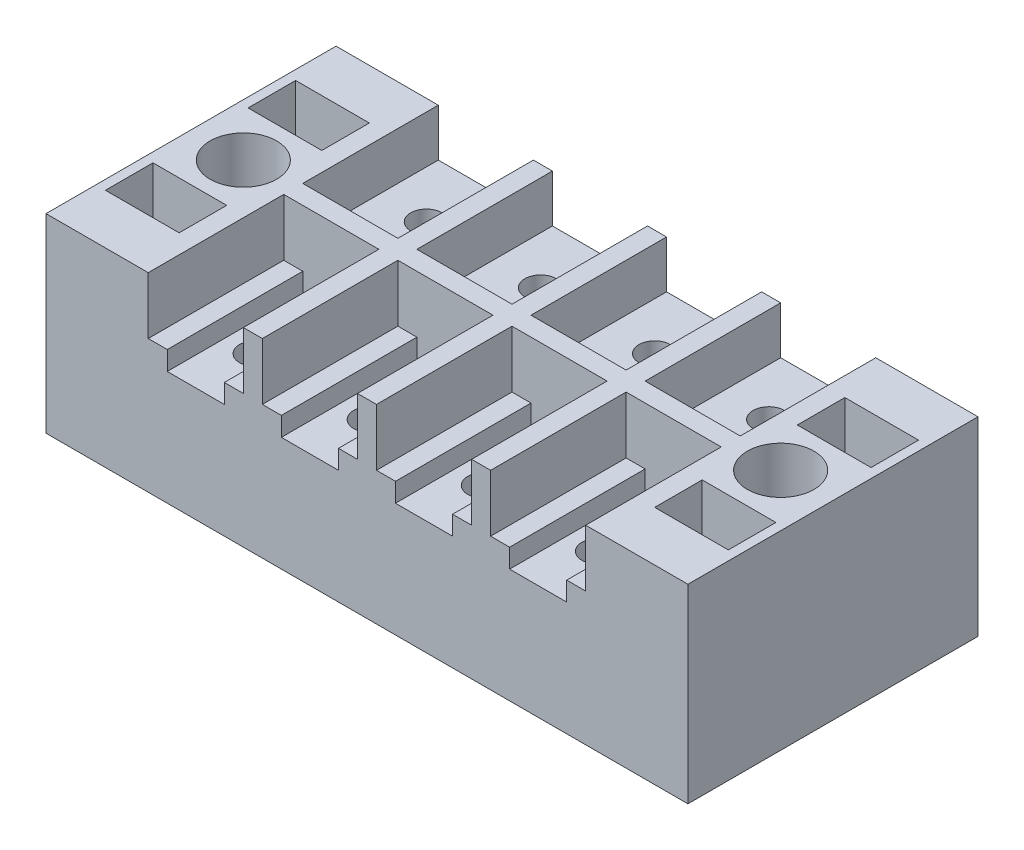
SolidWorks part; units mm, degrees
ref_plane "前视基准面" through (0, 0, 0) normal (0, 0, 1) x (1, 0, 0)
ref_plane "上视基准面" through (0, 0, 0) normal (0, 1, 0) x (1, 0, 0)
ref_plane "右视基准面" through (0, 0, 0) normal (1, 0, 0) x (0, 0, -1)
other "Configuration Table"
sketch "草图1" plane through (0, 0, 0) normal (0, 1, 0) x (1, 0, 0)
  line L0 (-57.3899, 0) -> (47.4284, 0) construction
  line L1 (33.75, -15.25) -> (-33.75, -15.25)
  line L2 (33.75, -15.25) -> (33.75, 15.25)
  line L3 (33.75, 15.25) -> (-33.75, 15.25)
  line L4 (-33.75, -15.25) -> (-33.75, 15.25)
  line L5 (33.75, -15.25) -> (-33.75, 15.25) construction
  line L6 (33.75, 15.25) -> (-33.75, -15.25) construction
  line L7 (0, 27.679) -> (0, -18.5105) construction
  line L8 (-13, -1) -> (-13, -15.25)
  line L9 (-23, -1) -> (-13, -1)
  line L10 (-1, 15.25) -> (-1, 1)
  line L11 (1, 15.25) -> (1, 1)
  line L12 (-12, 15.25) -> (-12, -15.25) construction
  line L13 (12, 15.25) -> (12, -15.25) construction
  line L14 (-24, 15.25) -> (-24, -15.25) construction
  line L15 (24, 15.25) -> (24, -15.25) construction
  line L16 (-23, 15.25) -> (-23, -15.25)
  line L17 (-13, 15.25) -> (-13, 1)
  line L18 (-25, 15.25) -> (-25, 1.299)
  line L19 (-11, 15.25) -> (-11, 1)
  line L20 (25, 15.25) -> (25, 1.299)
  line L21 (23, 15.25) -> (23, -15.25)
  line L22 (13, 15.25) -> (13, 1)
  line L23 (11, 15.25) -> (11, 1)
  line L24 (-25, -1.299) -> (-25, -15.25)
  line L25 (-23, 1) -> (-13, 1)
  line L26 (-11, 1) -> (-1, 1)
  line L27 (-11, -1) -> (-11, -15.25)
  line L28 (-11, -1) -> (-1, -1)
  line L29 (1, -1) -> (11, -1)
  line L30 (-1, -1) -> (-1, -15.25)
  line L31 (1, -1) -> (1, -15.25)
  line L32 (1, 1) -> (11, 1)
  line L33 (11, -1) -> (11, -15.25)
  line L34 (13, 1) -> (23, 1)
  line L35 (13, -1) -> (13, -15.25)
  line L36 (25, -1.299) -> (25, -15.25)
  line L37 (13, -1) -> (23, -1)
  line L38 (-32.75, -10) -> (-25, -10)
  line L39 (-32.75, 5) -> (-25, 5)
  line L40 (-32.75, 5) -> (-32.75, 10)
  line L41 (-32.75, 10) -> (-25, 10)
  line L42 (-25, 5) -> (-25, 10)
  line L43 (-25, -5) -> (-25, -10)
  line L44 (-32.75, -5) -> (-25, -5)
  line L45 (-32.75, -5) -> (-32.75, -10)
  line L46 (32.75, 10) -> (25, 10)
  line L47 (25, 5) -> (25, 10)
  line L48 (32.75, 5) -> (25, 5)
  line L49 (32.75, 5) -> (32.75, 10)
  line L50 (32.75, -5) -> (32.75, -10)
  line L51 (32.75, -5) -> (25, -5)
  line L52 (25, -5) -> (25, -10)
  line L53 (32.75, -10) -> (25, -10)
  line L54 (-18, 1) -> (-18, 16.7554) construction
  line L55 (-18, 1) -> (-18, -15.8397) construction
  line L56 (-6, 1) -> (-6, 16.7554) construction
  line L57 (-6, 1) -> (-6, -15.8397) construction
  line L58 (6, 1) -> (6, 16.7554) construction
  line L59 (6, 1) -> (6, -15.8397) construction
  line L60 (18, 1) -> (18, 16.7554) construction
  line L61 (18, 1) -> (18, -15.8397) construction
  circle A0 centre (-28.25, 0) radius 3.5
  circle A1 centre (-28.25, 0) radius 2.1
  circle A2 centre (28.25, 0) radius 2.1
  circle A3 centre (28.25, 0) radius 3.5
  point P0 (0, 0)
  dimension "D3" = 7
  dimension "D4" = 4.2
  dimension "D1" = 67.5
  dimension "D2" = 30.5
  dimension "D5" = 56.5
  dimension "D6" = 1
  dimension "D7" = 2
  dimension "D8" = 12
  dimension "D9" = 5
  dimension "D10" = 10
extrude "凸台-拉伸1" add sketch "草图1" against normal blind 20 contours L3 L4 L1 L2 | L40 L39 L42 L41 | L38 L43 L44 L45 | L50 L53 L52 L51 | L46 L47 L48 L49
extrude "切除-拉伸1" cut sketch "草图1<3>" against normal blind 13 contours A0 | A3
sketch "草图1<3>" plane through (0, 0, 0) normal (0, 1, 0) x (1, 0, 0) same geometry as "草图1"
extrude "切除-拉伸2" cut sketch "草图1<4>" against normal through all contours A1 | A2
sketch "草图1<4>" plane through (0, 0, 0) normal (0, 1, 0) x (1, 0, 0) same geometry as "草图1"
extrude "切除-拉伸3" cut sketch "草图1<5>" against normal blind 6 contours L9 L16 L1 L8 | L30 L28 L27 L1 | L33 L29 L31 L1 | L37 L35 L1 L21 region at (18, 0, 8.125) region at (6, 0, 8.125) region at (-6, 0, 8.125) region at (-18, 0, 8.125)
sketch "草图1<5>" plane through (0, 0, 0) normal (0, 1, 0) x (1, 0, 0) same geometry as "草图1"
extrude "切除-拉伸4" cut sketch "草图1<6>" against normal blind 5 contours L16 L25 L17 L3 | L19 L26 L10 L3 | L11 L32 L23 L3 | L22 L34 L21 L3 region at (18, 0, -8.125) region at (6, 0, -8.125) region at (-6, 0, -8.125) region at (-18, 0, -8.125)
sketch "草图1<6>" plane through (0, 0, 0) normal (0, 1, 0) x (1, 0, 0) same geometry as "草图1"
sketch "草图2" plane through (0, 0, 15.25) normal (0, 0, 1) x (1, 0, 0)
  line L0 (-18, -6) -> (-18, -7.8376) construction
  line L1 (-13, -6) -> (-23, -6) construction
  line L2 (-9, -6) -> (-9, -8)
  line L3 (-21, -6) -> (-15, -6)
  line L4 (-21, -6) -> (-21, -8)
  line L5 (-21, -8) -> (-15, -8)
  line L6 (-15, -6) -> (-15, -8)
  line L7 (-9, -6) -> (-3, -6)
  line L8 (-3, -6) -> (-3, -8)
  line L9 (-9, -8) -> (-3, -8)
  line L10 (3, -6) -> (3, -8)
  line L11 (3, -6) -> (9, -6)
  line L12 (9, -6) -> (9, -8)
  line L13 (3, -8) -> (9, -8)
  line L14 (15, -6) -> (15, -8)
  line L15 (15, -6) -> (21, -6)
  line L16 (21, -6) -> (21, -8)
  line L17 (15, -8) -> (21, -8)
  dimension "D1" = 6
  dimension "D2" = 2
  dimension "D3" = 4
extrude "切除-拉伸5" cut sketch "草图2" against normal up to surface (14.25 mm away) up to face at (-18, -3, 1)
sketch "草图3" plane through (0, -20, 0) normal (0, -1, 0) x (1, 0, 0)
  line L5 (33.75, 15.25) -> (-33.75, 15.25) construction
  line L6 (-23, -15.25) -> (-23, 15.25) construction
  line L8 (-18, 1) -> (-18, 15.25) construction
  line L9 (-23, 1) -> (-13, 1) construction
  line L10 (-23, 3.75) -> (23, 3.75)
  line L11 (-23, 3.75) -> (-23, 13.75)
  line L12 (-23, 13.75) -> (23, 13.75)
  line L13 (23, 3.75) -> (23, 13.75)
  line L14 (23, -15.25) -> (23, 15.25) construction
  line L15 (-35.8054, 0) -> (37.4721, 0) construction
  line L16 (-57.3899, 0) -> (47.4284, 0) construction
  line L17 (-23, -13.75) -> (23, -13.75)
  line L18 (23, -3.75) -> (23, -13.75)
  line L19 (-23, -3.75) -> (23, -3.75)
  line L20 (-23, -3.75) -> (-23, -13.75)
  line L22 (-23, -2.55) -> (23, -2.55)
  line L23 (-23, -2.55) -> (-23, 2.55)
  line L24 (-23, 2.55) -> (23, 2.55)
  line L25 (23, -2.55) -> (23, 2.55)
  circle A0 centre (-18, 9.25) radius 3.5
  circle A1 centre (-6, 9.25) radius 3.5
  circle A2 centre (6, 9.25) radius 3.5
  circle A3 centre (18, 9.25) radius 3.5
  circle A4 centre (-6, -8.25) radius 3.5
  circle A5 centre (6, -8.25) radius 3.5
  circle A6 centre (18, -8.25) radius 3.5
  circle A7 centre (-18, -8.25) radius 3.5
  dimension "D1" = 7
  dimension "D2" = 6
  dimension "D3" = 4
  dimension "D5" = 1.5
  dimension "D6" = 10
  dimension "D7" = 1.2
  dimension "D4" = 2
extrude "切除-拉伸6" cut sketch "草图3" against normal blind 7.5 contours L10 L13 L12 L11 A3 A2 A1 A0 | L19 L20 L17 L18 A7 A6 A5 A4 region at (0, -20, 8.4985) region at (0, -20, -9.0015)
extrude "切除-拉伸7" cut sketch "草图3<3>" against normal blind 9.5 contours L22 L25 L24 L23 region at (0, -20, 0)
sketch "草图3<3>" plane through (0, -20, 0) normal (0, -1, 0) x (1, 0, 0) same geometry as "草图3"
sketch "草图4" plane through (0, -12.5, 0) normal (0, -1, 0) x (1, 0, 0)
  line L0 (-23, 3.75) -> (23, 3.75) construction
  line L1 (-22, 3.75) -> (-14, 3.75)
  line L2 (-22, 3.75) -> (-22, 13.75)
  line L3 (-22, 13.75) -> (-14, 13.75)
  line L4 (-14, 3.75) -> (-14, 13.75)
  line L5 (-23, 13.75) -> (23, 13.75) construction
  line L6 (-18, 12.75) -> (-18, 5.75) construction
  line L7 (-10, 3.75) -> (-10, 13.75)
  line L8 (-10, 3.75) -> (-2, 3.75)
  line L9 (-2, 3.75) -> (-2, 13.75)
  line L10 (-10, 13.75) -> (-2, 13.75)
  line L11 (2, 3.75) -> (2, 13.75)
  line L12 (2, 3.75) -> (10, 3.75)
  line L13 (10, 3.75) -> (10, 13.75)
  line L14 (2, 13.75) -> (10, 13.75)
  line L15 (14, 3.75) -> (14, 13.75)
  line L16 (14, 3.75) -> (22, 3.75)
  line L17 (22, 3.75) -> (22, 13.75)
  line L18 (14, 13.75) -> (22, 13.75)
  line L19 (-10, -13.75) -> (-10, -3.75)
  line L20 (-10, -13.75) -> (-2, -13.75)
  line L21 (-2, -13.75) -> (-2, -3.75)
  line L22 (-10, -3.75) -> (-2, -3.75)
  line L23 (2, -13.75) -> (2, -3.75)
  line L24 (2, -13.75) -> (10, -13.75)
  line L25 (10, -13.75) -> (10, -3.75)
  line L26 (2, -3.75) -> (10, -3.75)
  line L27 (14, -13.75) -> (14, -3.75)
  line L28 (14, -13.75) -> (22, -13.75)
  line L29 (22, -13.75) -> (22, -3.75)
  line L30 (14, -3.75) -> (22, -3.75)
  line L31 (-22, -13.75) -> (-22, -3.75)
  line L32 (-22, -13.75) -> (-14, -13.75)
  line L33 (-14, -13.75) -> (-14, -3.75)
  line L34 (-22, -3.75) -> (-14, -3.75)
  circle A0 centre (-18, 9.25) radius 3.5 construction
  circle A1 centre (-18, 9.25) radius 3.5 construction
  dimension "D1" = 8
  dimension "D2" = 4
  dimension "D3" = 2
extrude "凸台-拉伸2" add sketch "草图4" along normal blind 2.5
hole_wizard "M4 螺纹孔1" positions "草图5" profile "草图6" tap size "M4" standard "GB"
sketch "草图5" plane through (0, -5, 0) normal (0, 1, 0) x (1, 0, 0)
  line L0 (-18, 1) -> (-18, -15.8397) construction
  line L1 (-6, 1) -> (-6, -15.8397) construction
  line L2 (6, 1) -> (6, -15.8397) construction
  line L3 (18, 1) -> (18, -15.8397) construction
  line L4 (18, 1) -> (18, 16.7554) construction
  line L5 (6, 1) -> (6, 16.7554) construction
  line L6 (-6, 1) -> (-6, 16.7554) construction
  line L7 (-18, 1) -> (-18, 16.7554) construction
  line L8 (-18, 1) -> (-18, -15.8397) construction
  line L9 (-6, 1) -> (-6, -15.8397) construction
  line L10 (6, 1) -> (6, -15.8397) construction
  line L11 (18, 1) -> (18, -15.8397) construction
  line L12 (18, 1) -> (18, 16.7554) construction
  line L13 (6, 1) -> (6, 16.7554) construction
  line L14 (-6, 1) -> (-6, 16.7554) construction
  line L15 (-18, 1) -> (-18, 16.7554) construction
  line L17 (-57.3899, 0) -> (47.4284, 0) construction
  line L18 (-57.3899, 0) -> (47.4284, 0) construction
  point P0 (-18, 9)
  point P2 (-6, 9)
  point P4 (6, 9)
  point P6 (18, 9)
  point P8 (18, -9)
  point P10 (6, -9)
  point P12 (-6, -9)
  point P14 (-18, -9)
  point P17 (-19.4604, 2.1668)
  point P34 (0, 0)
  point P35 (0, 0)
  point P36 (0, 0)
  point P37 (0, 0)
  point P38 (0, 0)
  point P39 (0, 0)
  point P40 (0, 0)
  point P41 (0, 0)
  point P44 (0, 0)
  point P47 (0, 0)
  point P48 (0, 0)
  point P49 (0, 0)
  point P50 (0, 0)
  point P51 (0, 0)
  dimension "D1" = 18
  dimension "D2" = 18
  dimension "D3" = 18
  dimension "D4" = 18
sketch "草图6" plane through (-18, -5, -9) normal (1, 0, 0) x (0, 0, 1)
  line L0 (0, 0) -> (0, 11.0914)
  line L1 (0, 11.0914) -> (1.65, 10.1)
  line L2 (1.65, 10.1) -> (1.65, 0)
  line L5 (1.65, 0) -> (0, 0)
  line L10 (0, 11.0914) -> (-1.65, 10.1) construction
  line L11 (0, -6.35) -> (0, 107.95) construction
  dimension "螺纹孔钻头直径" = 3.3
  dimension "螺纹孔钻头深度" = 10.1
  dimension "导头角度" = 118
cosmetic thread "孔螺蚊线1" parameters "D1"=8, "D2"=4
cosmetic thread "孔螺蚊线2" parameters "D1"=8, "D2"=4
cosmetic thread "孔螺蚊线3" parameters "D1"=8, "D2"=4
cosmetic thread "孔螺蚊线4" parameters "D1"=8, "D2"=4
cosmetic thread "孔螺蚊线5" parameters "D1"=8, "D2"=4
cosmetic thread "孔螺蚊线6" parameters "D1"=8, "D2"=4
cosmetic thread "孔螺蚊线7" parameters "D1"=8, "D2"=4
cosmetic thread "孔螺蚊线8" parameters "D1"=8, "D2"=4
